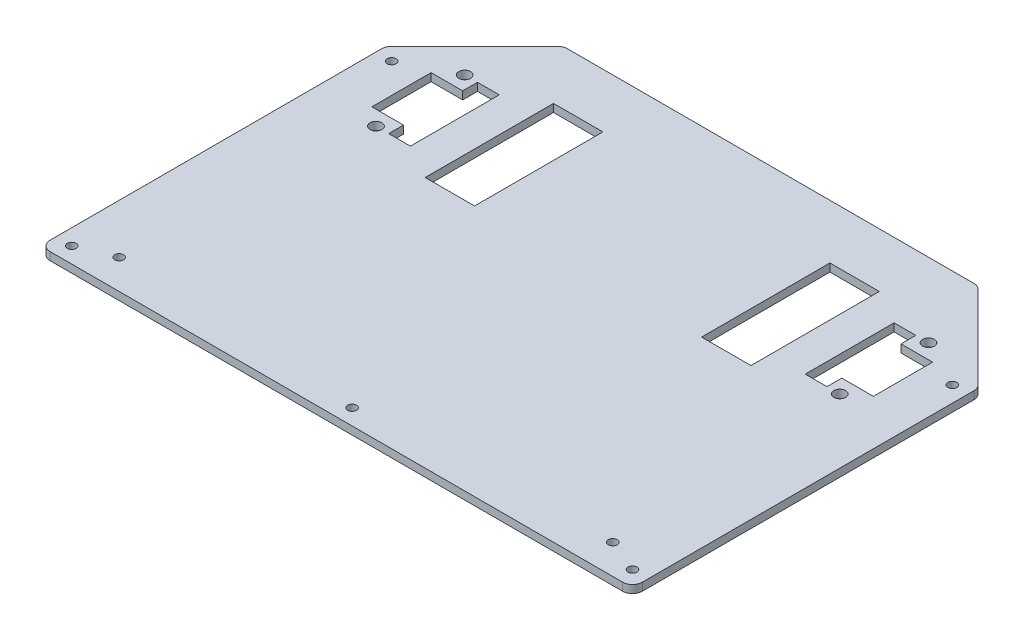
SolidWorks part; units mm, degrees
material "Acier non allié"
ref_plane "Front" through (0, 0, 0) normal (0, 0, 1) x (1, 0, 0)
ref_plane "Top" through (0, 0, 0) normal (0, 1, 0) x (1, 0, 0)
ref_plane "Right" through (0, 0, 0) normal (1, 0, 0) x (0, 0, -1)
sketch "Main scetch" plane through (0, 0, 0) normal (0, 1, 0) x (1, 0, 0)
  line L0 (-150, 0) -> (150, 0)
  line L1 (0, 0) -> (150, 0) construction
  line L2 (0, 0) -> (0, 220) construction
  line L3 (0, 220) -> (150, 220) construction
  line L4 (150, 0) -> (150, 220) construction
  line L5 (150, 0) -> (150, 175)
  line L6 (150, 175) -> (105, 220)
  line L10 (105, 220) -> (-105, 220)
  line L11 (-150, 0) -> (-150, 175)
  line L12 (-150, 175) -> (-105, 220)
  dimension "D1" = 150
  dimension "D2" = 220
  dimension "D3" = 45
  dimension "D4" = 45
extrude "Main extrusion" add sketch "Main scetch" along normal blind 4
fillet "Corner leave" radius 5 6 edges at (-150, 2, 0) (150, 2, -175) (105, 2, -220) (150, 2, 0) (-105, 2, -220) (-150, 2, -175)
sketch "Esquisse2" plane through (0, 4, 0) normal (0, 1, 0) x (1, 0, 0)
  line L0 (-145, 0) -> (145, 0) construction
  line L1 (150, 5) -> (150, 172.9289) construction
  line L2 (148.5355, 176.4645) -> (106.4645, 218.5355) construction
  line L3 (102.9289, 220) -> (-102.9289, 220) construction
  line L4 (-106.4645, 218.5355) -> (-148.5355, 176.4645) construction
  line L5 (-150, 172.9289) -> (-150, 5) construction
  line L6 (-145, 0) -> (145, 0) construction
  line L7 (150, 5) -> (150, 172.9289) construction
  line L8 (148.5355, 176.4645) -> (106.4645, 218.5355) construction
  line L9 (102.9289, 220) -> (-102.9289, 220) construction
  line L10 (-106.4645, 218.5355) -> (-148.5355, 176.4645) construction
  line L11 (-150, 172.9289) -> (-150, 5) construction
  line L12 (0, 0) -> (0, 238.9669) construction
  line L13 (0, 160) -> (165.6987, 160) construction
  line L14 (70, 230.4421) -> (70, 102.0601) construction
  line L15 (57.5, 192.5) -> (82.5, 192.5)
  line L16 (57.5, 192.5) -> (57.5, 127.5)
  line L17 (57.5, 127.5) -> (82.5, 127.5)
  line L18 (82.5, 192.5) -> (82.5, 127.5)
  line L19 (100, 137.5) -> (100, 182.5)
  line L20 (100, 182.5) -> (111, 182.5)
  line L22 (127, 175) -> (127, 145)
  line L23 (100, 137.5) -> (111, 137.5)
  line L35 (111, 182.5) -> (111, 175)
  line L36 (111, 175) -> (127, 175)
  line L37 (111, 137.5) -> (111, 145)
  line L38 (111, 145) -> (127, 145)
  line L39 (-111, 137.5) -> (-111, 145)
  line L40 (-100, 137.5) -> (-111, 137.5)
  line L41 (-100, 137.5) -> (-100, 182.5)
  line L42 (-100, 182.5) -> (-111, 182.5)
  line L43 (-111, 182.5) -> (-111, 175)
  line L44 (-111, 175) -> (-127, 175)
  line L45 (-127, 175) -> (-127, 145)
  line L46 (-111, 145) -> (-127, 145)
  line L47 (-57.5, 127.5) -> (-82.5, 127.5)
  line L48 (-82.5, 192.5) -> (-82.5, 127.5)
  line L49 (-57.5, 192.5) -> (-82.5, 192.5)
  line L50 (-57.5, 192.5) -> (-57.5, 127.5)
  circle A0 centre (117.47, 182.47) radius 3
  circle A1 centre (117.47, 137.53) radius 3
  circle A2 centre (-117.47, 137.53) radius 3
  circle A3 centre (-117.47, 182.47) radius 3
  point P28 (127, 160)
  point P29 (100, 160)
  dimension "D12" = 6
  dimension "D1" = 60
  dimension "D2" = 65
  dimension "D3" = 70
  dimension "D4" = 25
  dimension "D5" = 27
  dimension "D6" = 45
  dimension "D7" = 100
  dimension "D8" = 11
  dimension "D9" = 30
  dimension "D10" = 17.47
  dimension "D11" = 22.47
extrude "Enlèv. mat.-Extru.1" cut sketch "Esquisse2" against normal through all
sketch "Esquisse8" plane through (0, 4, 0) normal (0, 1, 0) x (1, 0, 0)
  line L0 (-150, 172.9289) -> (-150, 5) construction
  line L1 (-145, 0) -> (145, 0) construction
  line L3 (150, 5) -> (150, 172.9289) construction
  circle A0 centre (-125, 15) radius 1.5
  circle A1 centre (125, 15) radius 1.5
  dimension "D1" = 3
  dimension "D4" = 3
  dimension "D6" = 25
  dimension "D2" = 25
  dimension "D3" = 15
  dimension "D5" = 15
hole_wizard "Dégagement M41" positions "Esquisse16" profile "Esquisse17" hole size "M4" standard "ISO" end condition through all
sketch "Esquisse16" plane through (0, 4, 0) normal (0, 1, 0) x (1, 0, 0)
  point P0 (-125, 15)
  point P3 (125, 15)
sketch "Esquisse17" plane through (-125, 4, -15) normal (1, 0, 0) x (0, 0, 1)
  line L0 (0, 0) -> (0, 4)
  line L1 (0, 4) -> (2.25, 4)
  line L2 (2.25, 4) -> (2.25, 0)
  line L5 (2.25, 0) -> (0, 0)
  line L11 (0, -6.35) -> (0, 107.95) construction
  dimension "Diamètre du perçage jusqu'au prochain" = 4.5
  dimension "Profondeur du perçage jusqu'au prochain" = 4
sketch "Esquisse18" plane through (0, 4, 0) normal (0, 1, 0) x (1, 0, 0)
  line L0 (-150, 172.9289) -> (-150, 5) construction
  line L1 (-145, 0) -> (145, 0) construction
  line L3 (150, 5) -> (150, 172.9289) construction
  line L4 (0, 0) -> (0, 20.6924) construction
  circle A0 centre (-142, 8) radius 1
  circle A1 centre (-142, 170) radius 1
  circle A4 centre (142, 170) radius 1
  circle A5 centre (142, 8) radius 1
  circle A6 centre (0, 8) radius 1.5
  point P7 (-2.866, 8)
  dimension "D1" = 2
  dimension "D2" = 2
  dimension "D3" = 3
  dimension "D4" = 8
  dimension "D5" = 2
  dimension "D6" = 2
  dimension "D7" = 8
  dimension "D8" = 8
  dimension "D9" = 170
  dimension "D10" = 8
  dimension "D15" = 8
  dimension "D16" = 170
  dimension "D17" = 8
  dimension "D18" = 8
hole_wizard "Dégagement M42" positions "Esquisse19" profile "Esquisse20" hole size "M4" standard "ISO" end condition through all
sketch "Esquisse19" plane through (0, 4, 0) normal (0, 1, 0) x (1, 0, 0)
  point P0 (-142, 8)
  point P3 (0, 8)
  point P6 (142, 8)
  point P9 (142, 170)
  point P12 (-142, 170)
sketch "Esquisse20" plane through (-142, 4, -8) normal (1, 0, 0) x (0, 0, 1)
  line L0 (0, 0) -> (0, 4)
  line L1 (0, 4) -> (2.25, 4)
  line L2 (2.25, 4) -> (2.25, 0)
  line L5 (2.25, 0) -> (0, 0)
  line L11 (0, -6.35) -> (0, 107.95) construction
  dimension "Diamètre du perçage jusqu'au prochain" = 4.5
  dimension "Profondeur du perçage jusqu'au prochain" = 4
equation "\"WIDTH\"= 300mm'Total width of the robot"
equation "\"LENGTH\"= 220mm'Total length of the robot"
equation "\"D1@Main scetch\" = \"WIDTH\" / 2"
equation "\"D2@Main scetch\" = \"LENGTH\""
equation "\"CUT_DEPTH\"= 45mm'Depth of the cut on the edges of the plate"
equation "\"D3@Main scetch\" = \"CUT_DEPTH\""
equation "\"D4@Main scetch\" = \"CUT_DEPTH\""
equation "\"Plate_th\"= 3mm'Thickness of the plate"
equation "\"D1\"= \"Plate_th\""
